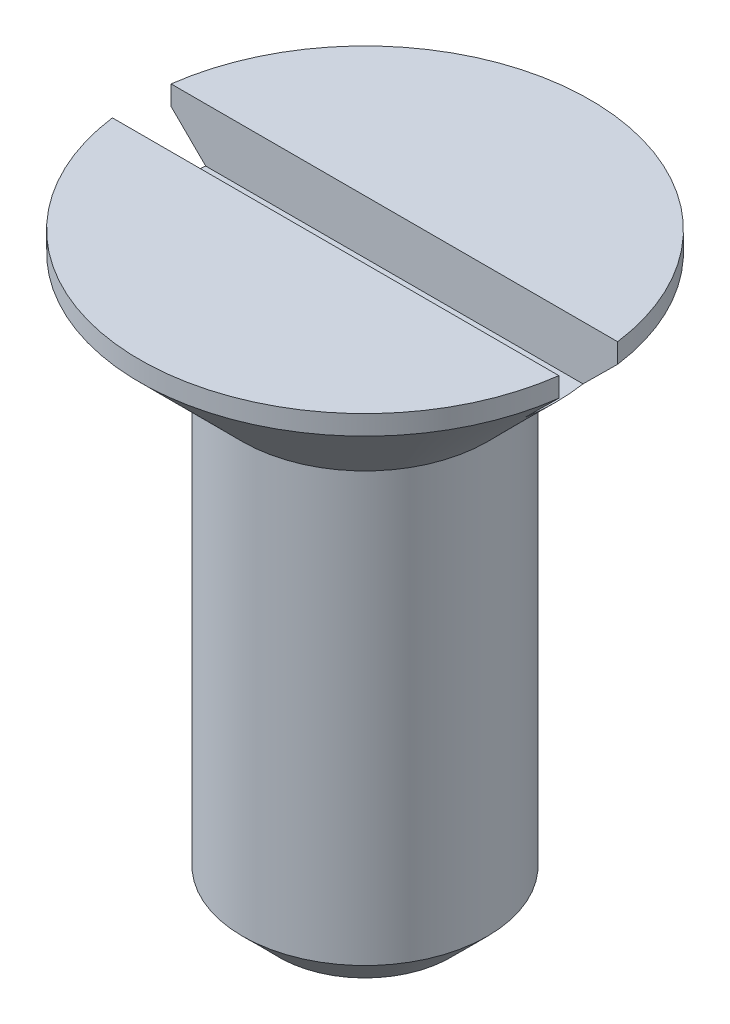
SolidWorks part; units mm, degrees
ref_plane "Спереди" through (0, 0, 0) normal (0, 0, 1) x (1, 0, 0)
ref_plane "Сверху" through (0, 0, 0) normal (0, 1, 0) x (1, 0, 0)
ref_plane "Справа" through (0, 0, 0) normal (1, 0, 0) x (0, 0, -1)
sketch "Эскиз1" plane through (0, 0, 0) normal (0, 0, 1) x (1, 0, 0)
  line L0 (0, 125.7632) -> (0, 0) construction
  line L2 (0, 92.035) -> (0, 80.035)
  line L3 (0, 92.035) -> (4.6, 92.035)
  line L4 (2.5, 89.535) -> (2.5, 80.035)
  line L5 (2.5, 89.535) -> (4.6, 91.635)
  line L6 (2.5, 80.035) -> (0, 80.035)
  line L7 (4.6, 92.035) -> (4.6, 91.635)
  dimension "D1" = 4.6
  dimension "D2" = 12
  dimension "D3" = 2.5
  dimension "D5" = 2.5
revolve "Повернуть1" add sketch "Эскиз1" angle 360 about L0
ref_axis "Ось4" through (0, 4.2936, 0) along (0, -1, 0)
sketch "Эскиз13" plane through (0, 92.035, 0) normal (0, 1, 0) x (-1, 0, 0)
  line L1 (4.6, -0.6) -> (-4.6, -0.6)
  line L2 (4.6, -0.6) -> (4.6, 0.6)
  line L3 (4.6, 0.6) -> (-4.6, 0.6)
  line L4 (-4.6, -0.6) -> (-4.6, 0.6)
  dimension "D1" = 4.6
  dimension "D2" = 9.2
  dimension "D3" = 0.6
  dimension "D4" = 1.2
extrude "Вырез-Вытянуть9" cut sketch "Эскиз13" against normal blind 1.1
chamfer "Фаска1" distance 0.75 angle 45 1 edges at (-2.5, 80.035, 0)
